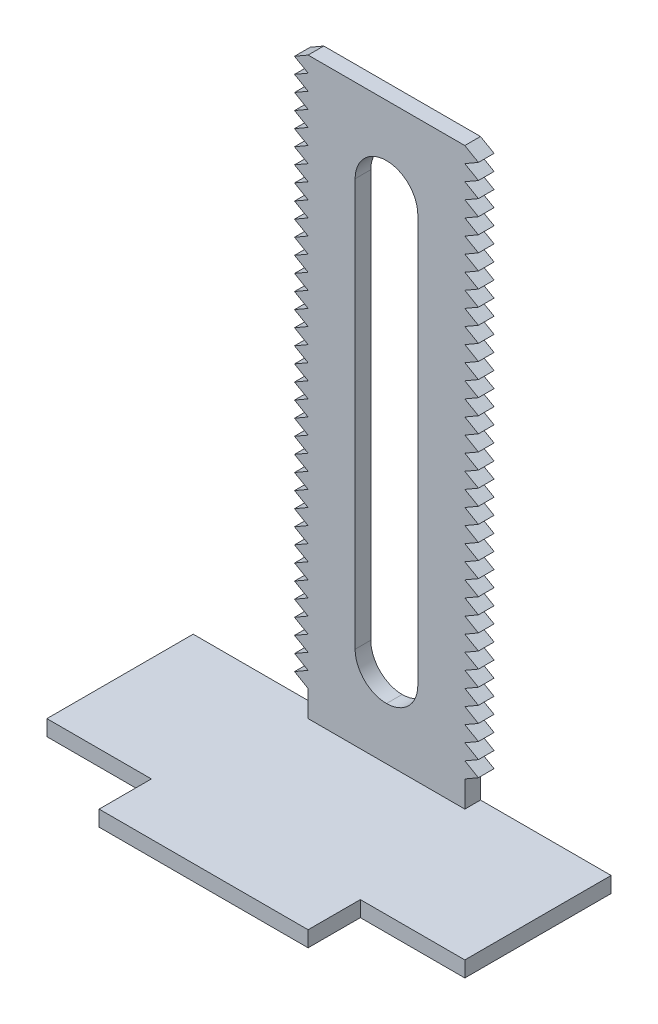
SolidWorks part; units mm, degrees
ref_plane "Front Plane" through (0, 0, 0) normal (0, 0, 1) x (1, 0, 0)
ref_plane "Top Plane" through (0, 0, 0) normal (0, 1, 0) x (1, 0, 0)
ref_plane "Right Plane" through (0, 0, 0) normal (1, 0, 0) x (0, 0, -1)
sketch "Sketch2" plane through (0, 0, 0) normal (0, 1, 0) x (1, 0, 0)
  line L1 (-15, 1.5) -> (15, 1.5)
  line L2 (-15, 1.5) -> (-15, -1.5)
  line L3 (-15, -1.5) -> (15, -1.5)
  line L4 (15, 1.5) -> (15, -1.5)
  line L5 (-15, 1.5) -> (15, -1.5) construction
  line L6 (-15, -1.5) -> (15, 1.5) construction
  point P0 (0, 0)
  dimension "D1" = 30
  dimension "D2" = 3
extrude "Boss-Extrude1" add sketch "Sketch2" along normal blind 110
sketch "Sketch3" plane through (0, 0, 1.5) normal (0, 0, 1) x (1, 0, 0)
  line L0 (15, 110) -> (17.5981, 108.5)
  line L1 (17.5981, 108.5) -> (15, 107)
  line L2 (15, 110) -> (15, 0) construction
  line L3 (15, 107) -> (15, 110)
  line L4 (15, 110) -> (15, 107)
  line L5 (15, 104) -> (15, 107)
  line L6 (17.5981, 105.5) -> (15, 104)
  line L7 (15, 107) -> (17.5981, 105.5)
  line L8 (15, 101) -> (15, 104)
  line L9 (17.5981, 102.5) -> (15, 101)
  line L10 (15, 104) -> (17.5981, 102.5)
  line L11 (15, 98) -> (15, 101)
  line L12 (17.5981, 99.5) -> (15, 98)
  line L13 (15, 101) -> (17.5981, 99.5)
  line L14 (15, 95) -> (15, 98)
  line L15 (17.5981, 96.5) -> (15, 95)
  line L16 (15, 98) -> (17.5981, 96.5)
  line L17 (15, 92) -> (15, 95)
  line L18 (17.5981, 93.5) -> (15, 92)
  line L19 (15, 95) -> (17.5981, 93.5)
  line L20 (15, 89) -> (15, 92)
  line L21 (17.5981, 90.5) -> (15, 89)
  line L22 (15, 92) -> (17.5981, 90.5)
  line L23 (15, 86) -> (15, 89)
  line L24 (17.5981, 87.5) -> (15, 86)
  line L25 (15, 89) -> (17.5981, 87.5)
  line L26 (15, 83) -> (15, 86)
  line L27 (17.5981, 84.5) -> (15, 83)
  line L28 (15, 86) -> (17.5981, 84.5)
  line L29 (15, 80) -> (15, 83)
  line L30 (17.5981, 81.5) -> (15, 80)
  line L31 (15, 83) -> (17.5981, 81.5)
  line L32 (15, 77) -> (15, 80)
  line L33 (17.5981, 78.5) -> (15, 77)
  line L34 (15, 80) -> (17.5981, 78.5)
  line L35 (15, 74) -> (15, 77)
  line L36 (17.5981, 75.5) -> (15, 74)
  line L37 (15, 77) -> (17.5981, 75.5)
  line L38 (15, 71) -> (15, 74)
  line L39 (17.5981, 72.5) -> (15, 71)
  line L40 (15, 74) -> (17.5981, 72.5)
  line L41 (15, 68) -> (15, 71)
  line L42 (17.5981, 69.5) -> (15, 68)
  line L43 (15, 71) -> (17.5981, 69.5)
  line L44 (15, 65) -> (15, 68)
  line L45 (17.5981, 66.5) -> (15, 65)
  line L46 (15, 68) -> (17.5981, 66.5)
  line L47 (15, 62) -> (15, 65)
  line L48 (17.5981, 63.5) -> (15, 62)
  line L49 (15, 65) -> (17.5981, 63.5)
  line L50 (15, 59) -> (15, 62)
  line L51 (17.5981, 60.5) -> (15, 59)
  line L52 (15, 62) -> (17.5981, 60.5)
  line L53 (15, 56) -> (15, 59)
  line L54 (17.5981, 57.5) -> (15, 56)
  line L55 (15, 59) -> (17.5981, 57.5)
  line L56 (15, 53) -> (15, 56)
  line L57 (17.5981, 54.5) -> (15, 53)
  line L58 (15, 56) -> (17.5981, 54.5)
  line L59 (15, 50) -> (15, 53)
  line L60 (17.5981, 51.5) -> (15, 50)
  line L61 (15, 53) -> (17.5981, 51.5)
  line L62 (15, 47) -> (15, 50)
  line L63 (17.5981, 48.5) -> (15, 47)
  line L64 (15, 50) -> (17.5981, 48.5)
  line L65 (15, 44) -> (15, 47)
  line L66 (17.5981, 45.5) -> (15, 44)
  line L67 (15, 47) -> (17.5981, 45.5)
  line L68 (15, 41) -> (15, 44)
  line L69 (17.5981, 42.5) -> (15, 41)
  line L70 (15, 44) -> (17.5981, 42.5)
  line L71 (15, 38) -> (15, 41)
  line L72 (17.5981, 39.5) -> (15, 38)
  line L73 (15, 41) -> (17.5981, 39.5)
  line L74 (15, 35) -> (15, 38)
  line L75 (17.5981, 36.5) -> (15, 35)
  line L76 (15, 38) -> (17.5981, 36.5)
  line L77 (-15, 110) -> (-15, 0) construction
  line L78 (-15, 110) -> (-17.5981, 108.5)
  line L79 (-17.5981, 108.5) -> (-15, 107)
  line L80 (-15, 107) -> (-15, 110)
  line L81 (-17.5981, 105.5) -> (-15, 104)
  line L82 (-15, 107) -> (-17.5981, 105.5)
  line L83 (-15, 104) -> (-15, 107)
  line L84 (-17.5981, 102.5) -> (-15, 101)
  line L85 (-15, 104) -> (-17.5981, 102.5)
  line L86 (-15, 101) -> (-15, 104)
  line L87 (-17.5981, 99.5) -> (-15, 98)
  line L88 (-15, 101) -> (-17.5981, 99.5)
  line L89 (-15, 98) -> (-15, 101)
  line L90 (-17.5981, 96.5) -> (-15, 95)
  line L91 (-15, 98) -> (-17.5981, 96.5)
  line L92 (-15, 95) -> (-15, 98)
  line L93 (-17.5981, 93.5) -> (-15, 92)
  line L94 (-15, 95) -> (-17.5981, 93.5)
  line L95 (-15, 92) -> (-15, 95)
  line L96 (-17.5981, 90.5) -> (-15, 89)
  line L97 (-15, 92) -> (-17.5981, 90.5)
  line L98 (-15, 89) -> (-15, 92)
  line L99 (-17.5981, 87.5) -> (-15, 86)
  line L100 (-15, 89) -> (-17.5981, 87.5)
  line L101 (-15, 86) -> (-15, 89)
  line L102 (-17.5981, 84.5) -> (-15, 83)
  line L103 (-15, 86) -> (-17.5981, 84.5)
  line L104 (-15, 83) -> (-15, 86)
  line L105 (-17.5981, 81.5) -> (-15, 80)
  line L106 (-15, 83) -> (-17.5981, 81.5)
  line L107 (-15, 80) -> (-15, 83)
  line L108 (-17.5981, 78.5) -> (-15, 77)
  line L109 (-15, 80) -> (-17.5981, 78.5)
  line L110 (-15, 77) -> (-15, 80)
  line L111 (-17.5981, 75.5) -> (-15, 74)
  line L112 (-15, 77) -> (-17.5981, 75.5)
  line L113 (-15, 74) -> (-15, 77)
  line L114 (-17.5981, 72.5) -> (-15, 71)
  line L115 (-15, 74) -> (-17.5981, 72.5)
  line L116 (-15, 71) -> (-15, 74)
  line L117 (-17.5981, 69.5) -> (-15, 68)
  line L118 (-15, 71) -> (-17.5981, 69.5)
  line L119 (-15, 68) -> (-15, 71)
  line L120 (-17.5981, 66.5) -> (-15, 65)
  line L121 (-15, 68) -> (-17.5981, 66.5)
  line L122 (-15, 65) -> (-15, 68)
  line L123 (-17.5981, 63.5) -> (-15, 62)
  line L124 (-15, 65) -> (-17.5981, 63.5)
  line L125 (-15, 62) -> (-15, 65)
  line L126 (-17.5981, 60.5) -> (-15, 59)
  line L127 (-15, 62) -> (-17.5981, 60.5)
  line L128 (-15, 59) -> (-15, 62)
  line L129 (-17.5981, 57.5) -> (-15, 56)
  line L130 (-15, 59) -> (-17.5981, 57.5)
  line L131 (-15, 56) -> (-15, 59)
  line L132 (-17.5981, 54.5) -> (-15, 53)
  line L133 (-15, 56) -> (-17.5981, 54.5)
  line L134 (-15, 53) -> (-15, 56)
  line L135 (-17.5981, 51.5) -> (-15, 50)
  line L136 (-15, 53) -> (-17.5981, 51.5)
  line L137 (-15, 50) -> (-15, 53)
  line L138 (-17.5981, 48.5) -> (-15, 47)
  line L139 (-15, 50) -> (-17.5981, 48.5)
  line L140 (-15, 47) -> (-15, 50)
  line L141 (-17.5981, 45.5) -> (-15, 44)
  line L142 (-15, 47) -> (-17.5981, 45.5)
  line L143 (-15, 44) -> (-15, 47)
  line L144 (-17.5981, 42.5) -> (-15, 41)
  line L145 (-15, 44) -> (-17.5981, 42.5)
  line L146 (-15, 41) -> (-15, 44)
  line L147 (-17.5981, 39.5) -> (-15, 38)
  line L148 (-15, 41) -> (-17.5981, 39.5)
  line L149 (-15, 38) -> (-15, 41)
  line L150 (-17.5981, 36.5) -> (-15, 35)
  line L151 (-15, 38) -> (-17.5981, 36.5)
  line L152 (-15, 35) -> (-15, 38)
  line L153 (-17.5981, 33.5) -> (-15, 32)
  line L154 (-15, 35) -> (-17.5981, 33.5)
  line L155 (-15, 32) -> (-15, 35)
  line L156 (17.5981, 33.5) -> (15, 32)
  line L157 (15, 32) -> (15, 35)
  line L158 (15, 35) -> (17.5981, 33.5)
  line L159 (-17.5981, 30.5) -> (-15, 29)
  line L160 (-15, 32) -> (-17.5981, 30.5)
  line L161 (-15, 29) -> (-15, 32)
  line L162 (17.5981, 30.5) -> (15, 29)
  line L163 (15, 29) -> (15, 32)
  line L164 (15, 32) -> (17.5981, 30.5)
  line L165 (-17.5981, 27.5) -> (-15, 26)
  line L166 (-15, 29) -> (-17.5981, 27.5)
  line L167 (-15, 26) -> (-15, 29)
  line L168 (17.5981, 27.5) -> (15, 26)
  line L169 (15, 26) -> (15, 29)
  line L170 (15, 29) -> (17.5981, 27.5)
  line L171 (-17.5981, 24.5) -> (-15, 23)
  line L172 (-15, 26) -> (-17.5981, 24.5)
  line L173 (-15, 23) -> (-15, 26)
  line L174 (17.5981, 24.5) -> (15, 23)
  line L175 (15, 23) -> (15, 26)
  line L176 (15, 26) -> (17.5981, 24.5)
  line L177 (-17.5981, 21.5) -> (-15, 20)
  line L178 (-15, 23) -> (-17.5981, 21.5)
  line L179 (-15, 20) -> (-15, 23)
  line L180 (17.5981, 21.5) -> (15, 20)
  line L181 (15, 20) -> (15, 23)
  line L182 (15, 23) -> (17.5981, 21.5)
  line L183 (-17.5981, 18.5) -> (-15, 17)
  line L184 (-15, 20) -> (-17.5981, 18.5)
  line L185 (-15, 17) -> (-15, 20)
  line L186 (17.5981, 18.5) -> (15, 17)
  line L187 (15, 17) -> (15, 20)
  line L188 (15, 20) -> (17.5981, 18.5)
  line L189 (-17.5981, 15.5) -> (-15, 14)
  line L190 (-15, 17) -> (-17.5981, 15.5)
  line L191 (-15, 14) -> (-15, 17)
  line L192 (17.5981, 15.5) -> (15, 14)
  line L193 (15, 14) -> (15, 17)
  line L194 (15, 17) -> (17.5981, 15.5)
  line L195 (-17.5981, 12.5) -> (-15, 11)
  line L196 (-15, 14) -> (-17.5981, 12.5)
  line L197 (-15, 11) -> (-15, 14)
  line L198 (17.5981, 12.5) -> (15, 11)
  line L199 (15, 11) -> (15, 14)
  line L200 (15, 14) -> (17.5981, 12.5)
  line L201 (-17.5981, 9.5) -> (-15, 8)
  line L202 (-15, 11) -> (-17.5981, 9.5)
  line L203 (-15, 8) -> (-15, 11)
  line L204 (17.5981, 9.5) -> (15, 8)
  line L205 (15, 8) -> (15, 11)
  line L206 (15, 11) -> (17.5981, 9.5)
  line L207 (-17.5981, 6.5) -> (-15, 5)
  line L208 (-15, 8) -> (-17.5981, 6.5)
  line L209 (-15, 5) -> (-15, 8)
  line L210 (17.5981, 6.5) -> (15, 5)
  line L211 (15, 5) -> (15, 8)
  line L212 (15, 8) -> (17.5981, 6.5)
  line M152 (15, 0) -> (15, 110)
  line M154 (-15, 110) -> (-15, 0)
  dimension "D1" = 3
  dimension "D2" = 3
  dimension "D3" = 3
  dimension "D5" = 30
  dimension "D6" = 2.5981
  dimension "D7" = 3
  dimension "D8" = 3
  dimension "D9" = 3
  dimension "D11" = 30
  dimension "D12" = 2.5981
  dimension "D14" = 2.5981
  dimension "D4" = 25
  dimension "D10" = 25
  dimension "D13" = 11
extrude "Boss-Extrude2" add sketch "Sketch3" against normal blind 3 contours L78 L79 M154 | L82 L81 M154 | L85 L84 M154 | L88 L87 M154 | L91 L90 M154 | L94 L93 M154 | L97 L96 M154 | L100 L99 M154 | L103 L102 M154 | L106 L105 M154 | L109 L108 M154 | L1 L0 M152 | L7 L6 M152 | L10 L9 M152 | L13 L12 M152 | L16 L15 M152 | L19 L18 M152 | L22 L21 M152 | L25 L24 M152 | L28 L27 M152 | L31 L30 M152 | L34 L33 M152 | L112 L111 M154 | L115 L114 M154 | L118 L117 M154 | L121 L120 M154 | L124 L123 M154 | L127 L126 M154 | L130 L129 M154 | L133 L132 M154 | L136 L135 M154 | L139 L138 M154 | L142 L141 M154 | L145 L144 M154 | L148 L147 M154 | L151 L150 M154 | L37 L36 M152 | L43 L42 M152 | L46 L45 M152 | L49 L48 M152 | L61 L60 M152 | L64 L63 M152 | L67 L66 M152 | L70 L69 M152 | L73 L72 M152 | L158 L156 M152 | L164 L162 M152 | L154 L153 M154 | L160 L159 M154 | L166 L165 M154 | L172 L171 M154 | L178 L177 M154 | L184 L183 M154 | L170 L168 M152 | L176 L174 M152 | L190 L189 M154 | L182 L180 M152 | L188 L186 M152 | L196 L195 M154 | L194 L192 M152 | L200 L198 M152 | L206 L204 M152 | L212 L210 M152 | L208 L207 M154 | L202 L201 M154 | L40 L39 L38 | L52 L51 L50 | L55 L54 L53 | L58 L57 L56 | L76 L75 L74 region at (15.866, 6.5, 1.5) region at (15.866, 9.5, 1.5) region at (15.866, 12.5, 1.5) region at (15.866, 15.5, 1.5) region at (15.866, 18.5, 1.5) region at (15.866, 21.5, 1.5) region at (15.866, 24.5, 1.5) region at (15.866, 27.5, 1.5) region at (15.866, 30.5, 1.5) region at (15.866, 33.5, 1.5) region at (15.866, 39.5, 1.5) region at (15.866, 42.5, 1.5) region at (15.866, 45.5, 1.5) region at (15.866, 48.5, 1.5) region at (15.866, 51.5, 1.5) region at (15.866, 63.5, 1.5) region at (15.866, 66.5, 1.5) region at (15.866, 69.5, 1.5) region at (15.866, 75.5, 1.5) region at (15.866, 78.5, 1.5) region at (15.866, 81.5, 1.5) region at (15.866, 84.5, 1.5) region at (15.866, 87.5, 1.5) region at (15.866, 90.5, 1.5) region at (15.866, 93.5, 1.5) region at (15.866, 96.5, 1.5) region at (15.866, 99.5, 1.5) region at (15.866, 102.5, 1.5) region at (15.866, 105.5, 1.5) region at (15.866, 108.5, 1.5) region at (-15.866, 108.5, 1.5) region at (-15.866, 6.5, 1.5) region at (-15.866, 9.5, 1.5) region at (-15.866, 12.5, 1.5) region at (-15.866, 15.5, 1.5) region at (-15.866, 18.5, 1.5) region at (-15.866, 21.5, 1.5) region at (-15.866, 24.5, 1.5) region at (-15.866, 27.5, 1.5) region at (-15.866, 30.5, 1.5) region at (-15.866, 33.5, 1.5) region at (-15.866, 36.5, 1.5) region at (-15.866, 39.5, 1.5) region at (-15.866, 42.5, 1.5) region at (-15.866, 45.5, 1.5) region at (-15.866, 48.5, 1.5) region at (-15.866, 51.5, 1.5) region at (-15.866, 54.5, 1.5) region at (-15.866, 57.5, 1.5) region at (-15.866, 60.5, 1.5) region at (-15.866, 63.5, 1.5) region at (-15.866, 66.5, 1.5) region at (-15.866, 69.5, 1.5) region at (-15.866, 72.5, 1.5) region at (-15.866, 75.5, 1.5) region at (-15.866, 78.5, 1.5) region at (-15.866, 81.5, 1.5) region at (-15.866, 84.5, 1.5) region at (-15.866, 87.5, 1.5) region at (-15.866, 90.5, 1.5)
sketch "Sketch4" plane through (0, 0, 1.5) normal (0, 0, 1) x (1, 0, 0)
  line L0 (-9, 0) -> (-9, -3)
  line L1 (-15, 0) -> (15, 0)
  line L2 (-15, 0) -> (-15, -6)
  line L3 (-15, -6) -> (15, -6)
  line L4 (15, 0) -> (15, -6)
  line L5 (-15, 0) -> (-12, 0)
  line L6 (-15, 0) -> (-15, -3)
  line L7 (-15, -3) -> (-12, -3)
  line L8 (-12, 0) -> (-12, -3)
  line L9 (-12, -3) -> (-9, -3)
  line L10 (-6, 0) -> (-6, -3)
  line L11 (-9, -3) -> (-6, -3)
  line L12 (-3, 0) -> (-3, -3)
  line L13 (-6, -3) -> (-3, -3)
  line L14 (0, 0) -> (0, -3)
  line L15 (-3, -3) -> (0, -3)
  line L16 (3, 0) -> (3, -3)
  line L17 (0, -3) -> (3, -3)
  line L18 (6, 0) -> (6, -3)
  line L19 (3, -3) -> (6, -3)
  line L20 (9, 0) -> (9, -3)
  line L21 (6, -3) -> (9, -3)
  line L22 (12, 0) -> (12, -3)
  line L23 (9, -3) -> (12, -3)
  line L24 (15, 0) -> (15, -3)
  line L25 (12, -3) -> (15, -3)
  dimension "D1" = 6
  dimension "D2" = 30
  dimension "D3" = 3
  dimension "D4" = 3
  dimension "D6" = 6
  dimension "D7" = 3
  dimension "D5" = 10
extrude "Boss-Extrude3" add sketch "Sketch4" against normal blind 3 contours L25 L23 L21 L19 L17 L15 L13 L11 L9 L7 L2 L3 L4 | L8 L1 L2 L7 | L0 L11 L10 L1 | L12 L15 L14 L1 | L14 L17 L16 L1 | L18 L21 L20 L1 | L22 L25 L4 L1 region at (-7.5, -1.5, 1.5) region at (0, -4.5, 1.5) region at (-13.5, -1.5, 1.5) region at (-1.5, -1.5, 1.5) region at (1.5, -1.5, 1.5) region at (7.5, -1.5, 1.5) region at (13.5, -1.5, 1.5)
sketch "Sketch5" plane through (0, 0, -1.5) normal (0, 0, -1) x (-1, 0, 0)
  line L0 (-15, 5) -> (-15, -6) construction
  line L1 (-6, 100) -> (6, 100)
  line L2 (-6, 100) -> (-6, 10)
  line L3 (-6, 10) -> (6, 10)
  line L4 (6, 100) -> (6, 10)
  line L5 (15, -6) -> (-15, -6) construction
  dimension "D1" = 12
  dimension "D2" = 90
  dimension "D3" = 9
  dimension "D4" = 16
extrude "Cut-Extrude1" cut sketch "Sketch5" against normal blind 3
fillet "Fillet1" radius 6 4 edges at (-6, 10, 0) (6, 10, 0) (6, 100, 0) (-6, 100, 0)
sketch "Sketch7" plane through (0, 0, 1.5) normal (0, 0, 1) x (1, 0, 0)
  line L0 (-15, 5) -> (-15, -6) construction
  line L1 (-15, 0) -> (15, 0)
  line L2 (-15, 0) -> (-15, -3)
  line L3 (-15, -3) -> (15, -3)
  line L4 (15, 0) -> (15, -3)
  line L5 (15, 5) -> (15, -6) construction
  line L6 (-15, -6) -> (15, -6) construction
  line L8 (-15, 0) -> (-12, 0)
  line L9 (-15, 0) -> (-15, -3)
  line L10 (-15, -3) -> (-12, -3)
  line L11 (-12, 0) -> (-12, -3)
  line L12 (-12, -3) -> (-9, -3)
  line L13 (-12, -3) -> (-12, 0)
  line L14 (-12, 0) -> (-9, 0)
  line L15 (-9, -3) -> (-9, 0)
  line L16 (-9, 0) -> (-6, 0)
  line L17 (-9, 0) -> (-9, -3)
  line L18 (-9, -3) -> (-6, -3)
  line L19 (-6, 0) -> (-6, -3)
  line L20 (-6, -3) -> (-3, -3)
  line L21 (-6, -3) -> (-6, 0)
  line L22 (-6, 0) -> (-3, 0)
  line L23 (-3, -3) -> (-3, 0)
  line L24 (-3, 0) -> (3, 0)
  line L25 (-3, 0) -> (-3, -3)
  line L26 (-3, -3) -> (3, -3)
  line L27 (3, 0) -> (3, -3)
  line L28 (3, -3) -> (6, -3)
  line L29 (3, -3) -> (3, 0)
  line L30 (3, 0) -> (6, 0)
  line L31 (6, -3) -> (6, 0)
  line L32 (6, 0) -> (9, 0)
  line L33 (6, 0) -> (6, -3)
  line L34 (6, -3) -> (9, -3)
  line L35 (9, 0) -> (9, -3)
  line L36 (9, -3) -> (12, -3)
  line L37 (9, -3) -> (9, 0)
  line L38 (9, 0) -> (12, 0)
  line L39 (12, -3) -> (12, 0)
  line L40 (12, 0) -> (15, 0)
  line L41 (12, 0) -> (12, -3)
  line L42 (12, -3) -> (15, -3)
  line L43 (15, 0) -> (15, -3)
  dimension "D1" = 3
  dimension "D2" = 3
extrude "Boss-Extrude8" add sketch "Sketch7" along normal blind 10 contours L11 L1 L2 L3 | L19 L1 L15 L3 | L27 L1 L23 L3 | L35 L1 L31 L3 | L39 L3 L4 L1 region at (-13.5, -1.5, 1.5) region at (-7.5, -1.5, 1.5) region at (0, -1.5, 1.5) region at (7.5, -1.5, 1.5) region at (13.5, -1.5, 1.5)
sketch "Sketch8" plane through (-9, 0, 0) normal (-1, 0, 0) x (0, 0, 1)
  line L1 (-1.5, 0) -> (11.5, 0)
  line L2 (-1.5, 0) -> (-1.5, -3)
  line L3 (-1.5, -3) -> (11.5, -3)
  line L4 (11.5, 0) -> (11.5, -3)
extrude "Boss-Extrude9" add sketch "Sketch8" along normal blind 3
sketch "Sketch9" plane through (-3, 0, 0) normal (-1, 0, 0) x (0, 0, 1)
  line L1 (-1.5, 0) -> (11.5, 0)
  line L2 (-1.5, 0) -> (-1.5, -3)
  line L3 (-1.5, -3) -> (11.5, -3)
  line L4 (11.5, 0) -> (11.5, -3)
extrude "Boss-Extrude10" add sketch "Sketch9" along normal blind 3
sketch "Sketch10" plane through (6, 0, 0) normal (-1, 0, 0) x (0, 0, 1)
  line L1 (-1.5, 0) -> (11.5, 0)
  line L2 (-1.5, 0) -> (-1.5, -3)
  line L3 (-1.5, -3) -> (11.5, -3)
  line L4 (11.5, 0) -> (11.5, -3)
extrude "Boss-Extrude11" add sketch "Sketch10" along normal blind 3
sketch "Sketch11" plane through (12, 0, 0) normal (-1, 0, 0) x (0, 0, 1)
  line L1 (-1.5, 0) -> (11.5, 0)
  line L2 (-1.5, 0) -> (-1.5, -3)
  line L3 (-1.5, -3) -> (11.5, -3)
  line L4 (11.5, 0) -> (11.5, -3)
extrude "Boss-Extrude12" add sketch "Sketch11" along normal blind 3
sketch "Sketch12" plane through (-15, 0, 0) normal (-1, 0, 0) x (0, 0, 1)
  line L0 (-1.5, 5) -> (-1.5, -6) construction
  line L1 (11.5, 0) -> (-1.5, 0)
  line L2 (11.5, 0) -> (11.5, -3)
  line L3 (11.5, -3) -> (-1.5, -3)
  line L4 (-1.5, 0) -> (-1.5, -3)
  dimension "D1" = 3
extrude "Boss-Extrude13" add sketch "Sketch12" along normal blind 25
sketch "Sketch13" plane through (15, 0, 0) normal (1, 0, 0) x (0, 0, -1)
  line L0 (1.5, 5) -> (1.5, -6) construction
  line L1 (-11.5, 0) -> (1.5, 0)
  line L2 (-11.5, 0) -> (-11.5, -3)
  line L3 (-11.5, -3) -> (1.5, -3)
  line L4 (1.5, 0) -> (1.5, -3)
  dimension "D1" = 3
extrude "Boss-Extrude14" add sketch "Sketch13" along normal blind 25
sketch "Sketch14" plane through (0, 0, 11.5) normal (0, 0, 1) x (1, 0, 0)
  line L1 (-40, 0) -> (40, 0)
  line L2 (-40, 0) -> (-40, -3)
  line L3 (-40, -3) -> (40, -3)
  line L4 (40, 0) -> (40, -3)
extrude "Boss-Extrude15" add sketch "Sketch14" along normal blind 25
sketch "Sketch15" plane through (0, -3, 0) normal (0, -1, 0) x (1, 0, 0)
  line L0 (-40, 36.5) -> (40, 36.5) construction
  line L1 (-33, 36.5) -> (-30, 36.5)
  line L2 (-33, 36.5) -> (-33, -1.5)
  line L3 (-33, -1.5) -> (-30, -1.5)
  line L4 (-30, 36.5) -> (-30, -1.5)
  line L5 (-40, -1.5) -> (-15, -1.5) construction
  line L6 (-15, -1.5) -> (-15, 1.5) construction
  dimension "D1" = 3
  dimension "D2" = 15
extrude "Boss-Extrude16" add sketch "Sketch15" along normal blind 40
sketch "Sketch16" plane through (0, -3, 0) normal (0, -1, 0) x (1, 0, 0)
  line L0 (40, 36.5) -> (40, -1.5) construction
  line L1 (40, 20) -> (20, 20)
  line L2 (40, 20) -> (40, 15)
  line L3 (40, 15) -> (20, 15)
  line L4 (20, 20) -> (20, 15)
  line L7 (40, -1.5) -> (15, -1.5) construction
  dimension "D1" = 5
  dimension "D2" = 20
  dimension "D3" = 16.5
extrude "Cut-Extrude2" cut sketch "Sketch16" against normal blind 3
sketch "Sketch17" plane through (-30, 0, 0) normal (1, 0, 0) x (0, 0, -1)
  line L1 (-36.5, -43) -> (1.5, -43)
  line L2 (-36.5, -43) -> (-36.5, -3)
  line L3 (-36.5, -3) -> (1.5, -3)
  line L4 (1.5, -43) -> (1.5, -3)
extrude "Cut-Extrude3" cut sketch "Sketch17" against normal blind 3
sketch "Sketch19" plane through (0, 0, 1.5) normal (0, 0, 1) x (1, 0, 0)
  line L1 (-15, -3) -> (15, -3)
  line L2 (-15, -3) -> (-15, -6)
  line L3 (-15, -6) -> (15, -6)
  line L4 (15, -3) -> (15, -6)
extrude "Cut-Extrude4" cut sketch "Sketch19" against normal blind 3
sketch "Sketch20" plane through (20, 0, 0) normal (1, 0, 0) x (0, 0, -1)
  line L0 (-20, 0) -> (-15, 0) construction
  line L1 (-20, -3) -> (-15, -3)
  line L2 (-20, -3) -> (-20, 0)
  line L3 (-20, 0) -> (-15, 0)
  line L4 (-15, -3) -> (-15, 0)
extrude "Boss-Extrude17" add sketch "Sketch20" along normal up to surface (20 mm away) up to face at (40, -1.5, 28.25)
sketch "Sketch21" plane through (0, -3, 0) normal (0, -1, 0) x (-1, 0, 0)
  line L1 (40, -36.5) -> (20, -36.5)
  line L2 (40, -36.5) -> (40, -26.5)
  line L3 (40, -26.5) -> (20, -26.5)
  line L4 (20, -36.5) -> (20, -26.5)
  line L5 (-40, -36.5) -> (-20, -36.5)
  line L6 (-40, -36.5) -> (-40, -26.5)
  line L7 (-40, -26.5) -> (-20, -26.5)
  line L8 (-20, -36.5) -> (-20, -26.5)
  dimension "D1" = 20
  dimension "D2" = 10
  dimension "D3" = 20
  dimension "D4" = 10
extrude "Cut-Extrude5" cut sketch "Sketch21" against normal blind 3
